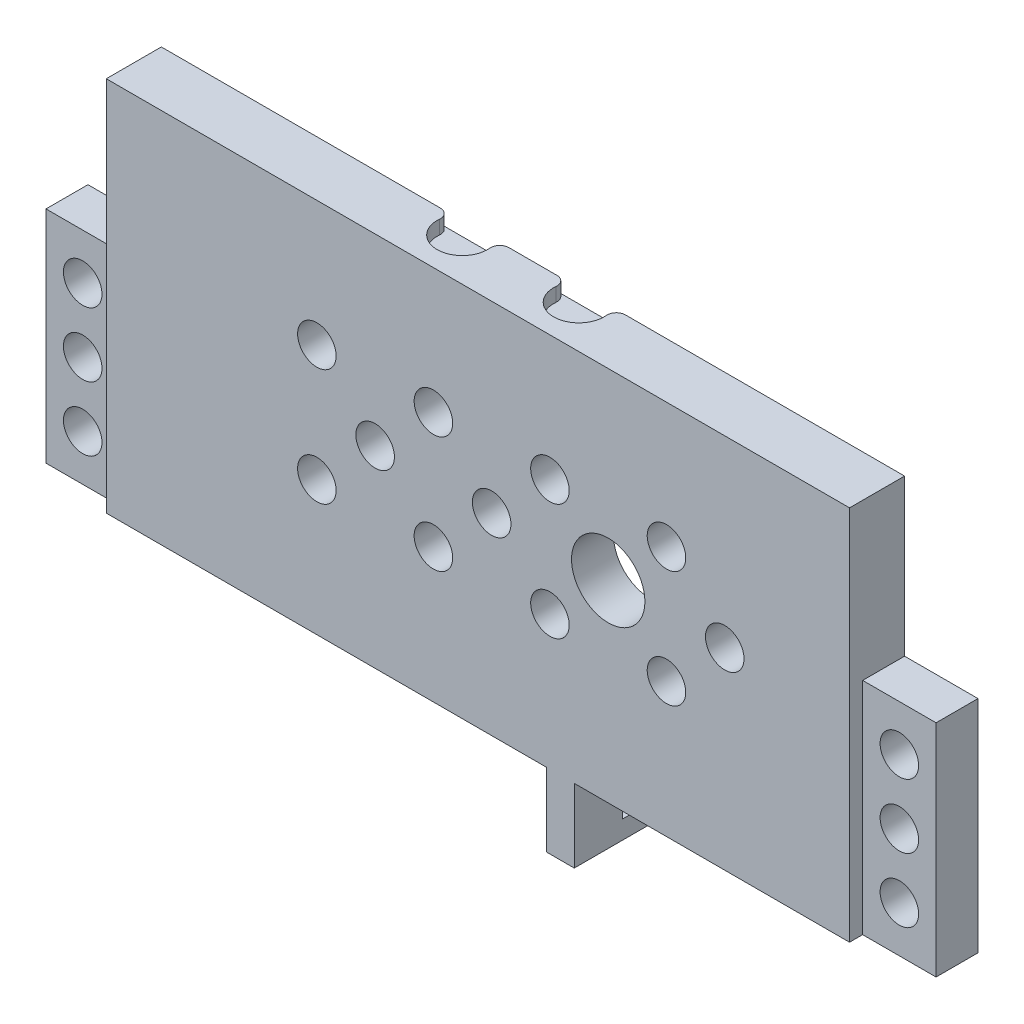
SolidWorks part; units mm, degrees
ref_plane "Front Plane" through (0, 0, 0) normal (0, 0, 1) x (1, 0, 0)
ref_plane "Top Plane" through (0, 0, 0) normal (0, 1, 0) x (1, 0, 0)
ref_plane "Right Plane" through (0, 0, 0) normal (1, 0, 0) x (0, 0, -1)
sketch "Sketch1" plane through (0, 0, 0) normal (0, 0, 1) x (1, 0, 0)
  line L1 (-40.5, -20.5) -> (40.5, -20.5)
  line L2 (-40.5, -20.5) -> (-40.5, 20.5)
  line L3 (-40.5, 20.5) -> (40.5, 20.5)
  line L4 (40.5, -20.5) -> (40.5, 20.5)
  line L5 (-40.5, -20.5) -> (40.5, 20.5) construction
  line L6 (-40.5, 20.5) -> (40.5, -20.5) construction
  point P0 (0, 0)
  dimension "D1" = 81
  dimension "D2" = 41
extrude "Boss-Extrude1" add sketch "Sketch1" along normal blind 6
sketch "Sketch5" plane through (0, 0, 0) normal (0, 0, -1) x (-1, 0, 0)
  line L1 (-37.5, -17.5) -> (37.5, -17.5)
  line L2 (-37.5, -17.5) -> (-37.5, 17.5)
  line L3 (-37.5, 17.5) -> (37.5, 17.5)
  line L4 (37.5, -17.5) -> (37.5, 17.5)
  line L5 (-37.5, -17.5) -> (37.5, 17.5) construction
  line L6 (-37.5, 17.5) -> (37.5, -17.5) construction
  point P0 (0, 0)
  dimension "D1" = 75
  dimension "D2" = 35
extrude "Cut-Extrude1" cut sketch "Sketch5" against normal blind 1.43
sketch "Sketch7" plane through (0, 0, 1.43) normal (0, 0, -1) x (-1, 0, 0)
  line L0 (37.5, 17.5) -> (-37.5, 17.5) construction
  line L1 (37.5, 17.5) -> (-37.5, 17.5) construction
  line L3 (37.5, -17.5) -> (37.5, 17.5) construction
  line L4 (-37.5, 17.5) -> (-37.5, -17.5) construction
  circle A0 centre (-14.2, 0.5) radius 2
  circle A1 centre (14.2, 0.5) radius 2
  dimension "D5" = 4
  dimension "D6" = 4
  dimension "D1" = 17
  dimension "D2" = 17
  dimension "D3" = 23.3
  dimension "D4" = 23.3
sketch "Sketch8" plane through (0, 0, 6) normal (0, 0, 1) x (1, 0, 0)
  circle A1 centre (26.9, 0.5) radius 2.1
  circle A2 centre (20.55, 6.8496) radius 2.1
  circle A3 centre (7.85, 6.8496) radius 2.1
  circle A4 centre (7.85, -5.8496) radius 2.1
  circle A5 centre (20.55, -5.8496) radius 2.1
  circle A6 centre (1.5, 0.5) radius 2.1
  circle A7 centre (-4.85, 6.8496) radius 2.1
  circle A8 centre (-4.85, -5.8496) radius 2.1
  circle A9 centre (-11.2, 0.5) radius 2.1
  circle A10 centre (-17.55, 6.8496) radius 2.1
  circle A11 centre (-17.55, -5.8496) radius 2.1
  circle A12 centre (14.2, 0.5) radius 4
  dimension "D2" = 4.2
  dimension "D3" = 4.2
  dimension "D4" = 4.2
  dimension "D5" = 4.2
  dimension "D6" = 4.2
  dimension "D7" = 4.2
  dimension "D8" = 4.2
  dimension "D9" = 4.2
  dimension "D10" = 4.2
  dimension "D11" = 4.2
  dimension "D16" = 4.2
  dimension "D20" = 8.98
  dimension "D12" = 8
  dimension "D14" = 8.98
  dimension "D15" = 8.98
  dimension "D17" = 8.98
  dimension "D19" = 8.98
  dimension "D21" = 8.98
  dimension "D22" = 8.98
  dimension "D23" = 12.7
  dimension "D24" = 12.7
extrude "Cut-Extrude2" cut sketch "Sketch8" against normal through all
sketch "Sketch9" plane through (0, 20.5, 0) normal (0, 1, 0) x (1, 0, 0)
  line L0 (0, 0) -> (12.55, 0)
  line L1 (40.5, 0) -> (-40.5, 0) construction
  line L2 (0, 0) -> (-12.55, 0)
  line L5 (-6.35, 0) -> (-6.35, -1.35)
  line L6 (6.35, 0) -> (6.35, -1.35)
  circle A4 centre (6.35, -1.35) radius 2.75
  circle A5 centre (-6.35, -1.35) radius 2.75
  dimension "D3" = 5.5
  dimension "D4" = 5.5
  dimension "D1" = 12.55
  dimension "D2" = 12.55
  dimension "D6" = 6.2
  dimension "D9" = 1.35
  dimension "D10" = 1.35
extrude "Cut-Extrude3" cut sketch "Sketch9" against normal blind 1.5 contours L2 | L0 region at (6.35, 20.5, 1.8327) region at (-6.35, 20.5, 1.8327)
fillet "Fillet1" radius 1 4 edges at (3.9542, 19.75, 0) (8.7458, 19.75, 0) (-3.9542, 19.75, 0) (-8.7458, 19.75, 0)
sketch "Sketch10" plane through (-40.5, 0, 0) normal (-1, 0, 0) x (0, 0, 1)
  line L1 (0, -20.5) -> (4.57, -20.5)
  line L2 (0, -20.5) -> (0, 3.5)
  line L3 (0, 3.5) -> (4.57, 3.5)
  line L4 (4.57, -20.5) -> (4.57, 3.5)
  dimension "D1" = 24
  dimension "D2" = 4.57
extrude "Boss-Extrude2" add sketch "Sketch10" along normal blind 8
sketch "Sketch12" plane through (40.5, 0, 0) normal (1, 0, 0) x (0, 0, -1)
  line L1 (0, -20.5) -> (-4.57, -20.5)
  line L2 (0, -20.5) -> (0, 3.5)
  line L3 (0, 3.5) -> (-4.57, 3.5)
  line L4 (-4.57, -20.5) -> (-4.57, 3.5)
  dimension "D1" = 24
  dimension "D2" = 4.57
extrude "Boss-Extrude3" add sketch "Sketch12" along normal blind 8
sketch "Sketch13" plane through (0, 0, 4.57) normal (0, 0, 1) x (1, 0, 0)
  line L0 (-44.5, 3.5) -> (-44.5, -20.5) construction
  line L1 (-48.5, 3.5) -> (-40.5, 3.5) construction
  line L2 (-48.5, -20.5) -> (-40.5, -20.5) construction
  line L3 (44.5, 3.5) -> (44.5, -20.5) construction
  line L4 (48.5, 3.5) -> (40.5, 3.5) construction
  line L5 (48.5, -20.5) -> (40.5, -20.5) construction
  circle A0 centre (-44.5, -8.5) radius 2.1
  circle A1 centre (-44.5, -1.5) radius 2.1
  circle A2 centre (-44.5, -15.5) radius 2.1
  circle A3 centre (44.5, -8.5) radius 2.1
  circle A4 centre (44.5, -1.5) radius 2.1
  circle A5 centre (44.5, -15.5) radius 2.1
  dimension "D1" = 4.2
  dimension "D2" = 4.2
  dimension "D3" = 4.2
  dimension "D4" = 4.2
  dimension "D5" = 4.2
  dimension "D6" = 4.2
  dimension "D7" = 7
  dimension "D8" = 7
  dimension "D9" = 7
  dimension "D10" = 7
extrude "Cut-Extrude4" cut sketch "Sketch13" against normal through all
sketch "Sketch14" plane through (0, -20.5, 0) normal (0, -1, 0) x (1, 0, 0)
  line L0 (0, 0) -> (7.5, 0)
  line L2 (-48.5, 0) -> (48.5, 0) construction
  line L3 (7.5, 0) -> (7.5, 6)
  line L4 (-40.5, 6) -> (40.5, 6) construction
  line L6 (7.5, 6) -> (10.5, 6)
  line L7 (7.5, 6) -> (7.5, -15)
  line L8 (7.5, -15) -> (10.5, -15)
  line L9 (10.5, 6) -> (10.5, -15)
  line M5 (-48.5, 0) -> (48.5, 0)
  line M9 (40.5, 6) -> (-40.5, 6)
  dimension "D1" = 7.5
  dimension "D2" = 3
  dimension "D3" = 21
extrude "Boss-Extrude4" add sketch "Sketch14" along normal blind 8 contours L9 L7 L8 M5 | L9 L3 M9 M5 region at (9, -20.5, -7.5) region at (9, -20.5, 3)
sketch "Sketch15" plane through (10.5, 0, 0) normal (1, 0, 0) x (0, 0, -1)
  line L0 (15, -28.5) -> (-6, -20.5) construction
  line L1 (-6, -28.5) -> (15, -20.5) construction
  line L3 (-0.75, -22.5) -> (9.75, -22.5)
  line L4 (-0.75, -22.5) -> (-0.75, -26.5)
  line L5 (-0.75, -26.5) -> (9.75, -26.5)
  line L6 (9.75, -22.5) -> (9.75, -26.5)
  line L7 (-0.75, -22.5) -> (9.75, -26.5) construction
  line L8 (-0.75, -26.5) -> (9.75, -22.5) construction
  point P8 (4.5, -24.5)
  dimension "D1" = 4
extrude "Cut-Extrude5" cut sketch "Sketch15" against normal through all
